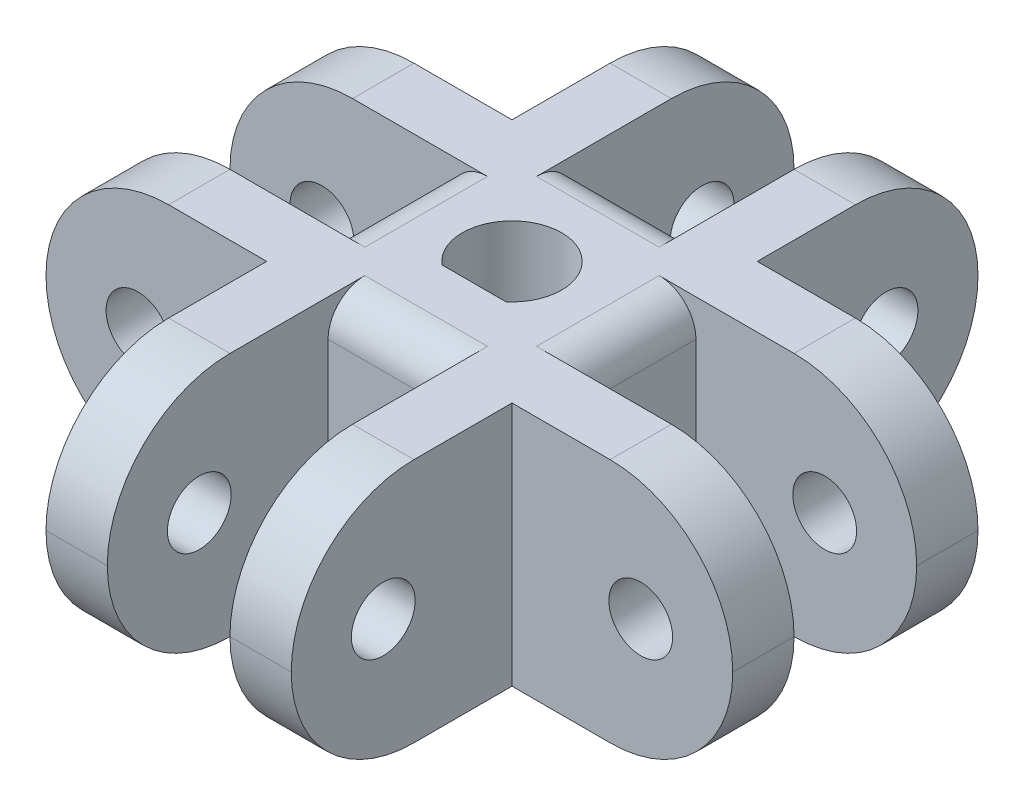
SolidWorks part; units mm, degrees
ref_plane "Front Plane" through (0, 0, 0) normal (0, 0, 1) x (1, 0, 0)
ref_plane "Top Plane" through (0, 0, 0) normal (0, 1, 0) x (1, 0, 0)
ref_plane "Right Plane" through (0, 0, 0) normal (1, 0, 0) x (0, 0, -1)
sketch "Sketch1" plane through (0, 0, 0) normal (0, 1, 0) x (1, 0, 0)
  line L1 (-2.6062, -3.1) -> (2.6062, -3.1)
  line L2 (-10, -10) -> (10, -10)
  line L21 (-10, -10) -> (-10, 10)
  line L22 (-10, 10) -> (10, 10)
  line L23 (10, -10) -> (10, 10)
  line L30 (-10, -10) -> (10, 10) construction
  line L31 (-10, 10) -> (10, -10) construction
  line L32 (-55, 0) -> (55, 0) construction
  line L33 (10, 10) -> (28, 10)
  line L34 (10, 10) -> (10, 5)
  line L35 (10, 5) -> (28, 5)
  line L36 (28, 10) -> (28, 5)
  line L37 (10, -5) -> (28, -5)
  line L38 (28, -10) -> (28, -5)
  line L39 (10, -10) -> (28, -10)
  line L40 (10, -10) -> (10, -5)
  line L41 (10, -10) -> (5, -10)
  line L42 (10, -10) -> (10, -28)
  line L43 (10, -28) -> (5, -28)
  line L44 (5, -10) -> (5, -28)
  line L45 (-10, -10) -> (-5, -10)
  line L46 (-5, -10) -> (-5, -28)
  line L47 (-10, -28) -> (-5, -28)
  line L48 (-10, -10) -> (-10, -28)
  line L49 (-10, -10) -> (-10, -5)
  line L50 (-10, -10) -> (-28, -10)
  line L51 (-28, -10) -> (-28, -5)
  line L52 (-10, -5) -> (-28, -5)
  line L53 (-10, 10) -> (-10, 5)
  line L54 (-10, 5) -> (-28, 5)
  line L55 (-28, 10) -> (-28, 5)
  line L56 (-10, 10) -> (-28, 10)
  line L57 (-10, 10) -> (-5, 10)
  line L58 (-10, 10) -> (-10, 28)
  line L59 (-10, 28) -> (-5, 28)
  line L60 (-5, 10) -> (-5, 28)
  line L61 (10, 10) -> (5, 10)
  line L62 (5, 10) -> (5, 28)
  line L63 (10, 28) -> (5, 28)
  line L64 (10, 10) -> (10, 28)
  arc A3 (2.6062, -3.1) -> (-2.6062, -3.1) centre (0, 0) ccw
  point P0 (0, 0)
  point P45 (0, 0)
  dimension "D1" = 20
  dimension "D3" = 3.1
  dimension "D4" = 18
  dimension "D2" = 8.1
  dimension "D5" = 5
  dimension "D6" = 4
extrude "Boss-Extrude1" add sketch "Sketch1" along normal blind 20 contours L2 L23 L22 L21 A3 L1 | L21 L52 L51 L50 | L21 L56 L55 L54 | L22 L60 L59 L58 | L22 L64 L63 L62 | L36 L33 L23 L35 | L23 L39 L38 L37 | L2 L44 L43 L42 | L2 L48 L47 L46 region at (-9.7172, 0, 7.5) region at (-19, 0, 7.5) region at (-7.5, 0, 19) region at (7.5, 0, 19) region at (-19, 0, -7.5) region at (19, 0, 7.5) region at (-7.5, 0, -19) region at (19, 0, -7.5) region at (7.5, 0, -19)
fillet "Fillet1" radius 10 16 edges at (-28, 0, 7.5) (-28, 0, -7.5) (-7.5, 0, -28) (7.5, 0, -28) (28, 0, -7.5) (28, 0, 7.5) (7.5, 0, 28) (-7.5, 0, 28) (-28, 20, 7.5) (-28, 20, -7.5) (-7.5, 20, -28) (7.5, 20, -28) (28, 20, -7.5) (28, 20, 7.5) (-7.5, 20, 28) (7.5, 20, 28)
sketch "Sketch2" plane through (0, 0, 10) normal (0, 0, 1) x (1, 0, 0)
  circle A0 centre (-20.5, 10) radius 2.6
  point P2 (0, 0)
  dimension "D2" = 5.2
  dimension "D1" = 7.5
extrude "Cut-Extrude1" cut sketch "Sketch2" against normal blind 20
ref_axis "Axis1" through (0, 21, 0) along (0, -1, 0)
pattern_circular "CirPattern1" count 4 over 360 about axis through (0, 21, 0) along (0, -1, 0) of "Cut-Extrude1"
fillet "Fillet2" radius 3 8 edges at (-10, 0, 0) (0, 0, -10) (10, 0, 0) (0, 0, 10) (-10, 20, 0) (0, 20, -10) (10, 20, 0) (0, 20, 10)
